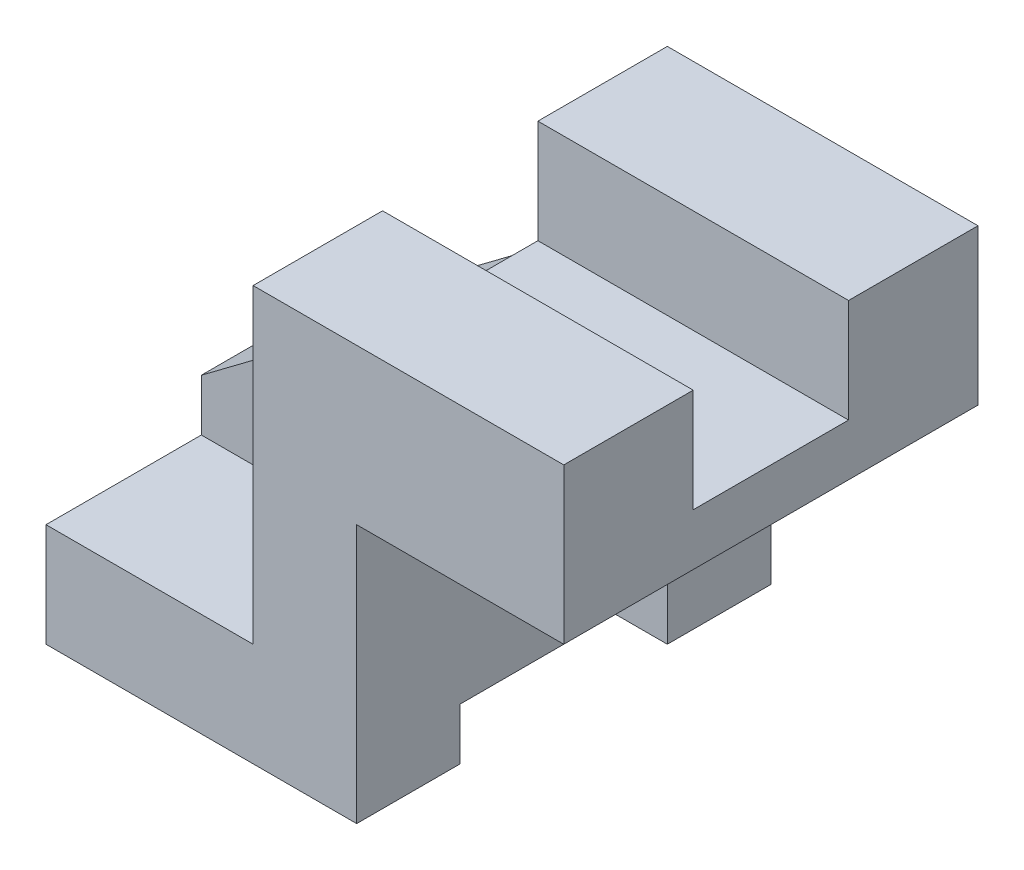
SolidWorks part; units mm, degrees
ref_plane "Front Plane" through (0, 0, 0) normal (0, 0, 1) x (1, 0, 0)
ref_plane "Top Plane" through (0, 0, 0) normal (0, 1, 0) x (1, 0, 0)
ref_plane "Right Plane" through (0, 0, 0) normal (1, 0, 0) x (0, 0, -1)
sketch "Sketch1" plane through (0, 0, 0) normal (0, 0, 1) x (1, 0, 0)
  line L0 (0, 0) -> (60, 0)
  line L1 (60, 0) -> (60, 50)
  line L2 (60, 50) -> (100, 50)
  line L3 (100, 50) -> (100, 80)
  line L4 (100, 80) -> (40, 80)
  line L5 (40, 80) -> (40, 20)
  line L6 (40, 20) -> (0, 20)
  line L7 (0, 20) -> (0, 0)
  line L8 (0, 20) -> (0, 30)
  line L9 (0, 30) -> (40, 60)
  dimension "D1" = 20
  dimension "D2" = 100
  dimension "D3" = 40
  dimension "D4" = 60
  dimension "D5" = 30
  dimension "D6" = 10
  dimension "D7" = 20
  dimension "D8" = 80
extrude "Boss-Extrude1" add sketch "Sketch1" along normal mid plane 80 contours L6 L7 L0 L1 L2 L3 L4 L5 region at (53.3333, 41.6667, 0)
extrude "Boss-Extrude2" add sketch "Sketch1<3>" along normal mid plane 20 contours L9 L8 L6 L5 region at (24, 34, 0)
sketch "Sketch1<3>" plane through (0, 0, 0) normal (0, 0, 1) x (1, 0, 0) same geometry as "Sketch1"
sketch "Sketch2" plane through (0, 0, 0) normal (1, 0, 0) x (0, 0, -1)
  line L0 (20, 0) -> (-20, 0)
  line L1 (-40, 0) -> (40, 0) construction
  line L2 (-20, 0) -> (-20, 10)
  line L3 (-20, 10) -> (20, 10)
  line L4 (20, 10) -> (20, 0)
  line L5 (15, 60) -> (-15, 60)
  line L7 (-15, 60) -> (-15, 80)
  line L8 (-40, 80) -> (40, 80) construction
  line L9 (-15, 80) -> (15, 80)
  line L10 (15, 80) -> (15, 60)
  point P0 (0, 0)
  point P6 (0, 0)
  point P11 (0, 60)
  dimension "D1" = 40
  dimension "D2" = 10
  dimension "D3" = 30
  dimension "D4" = 20
extrude "Cut-Extrude1" cut sketch "Sketch2" along normal through all
